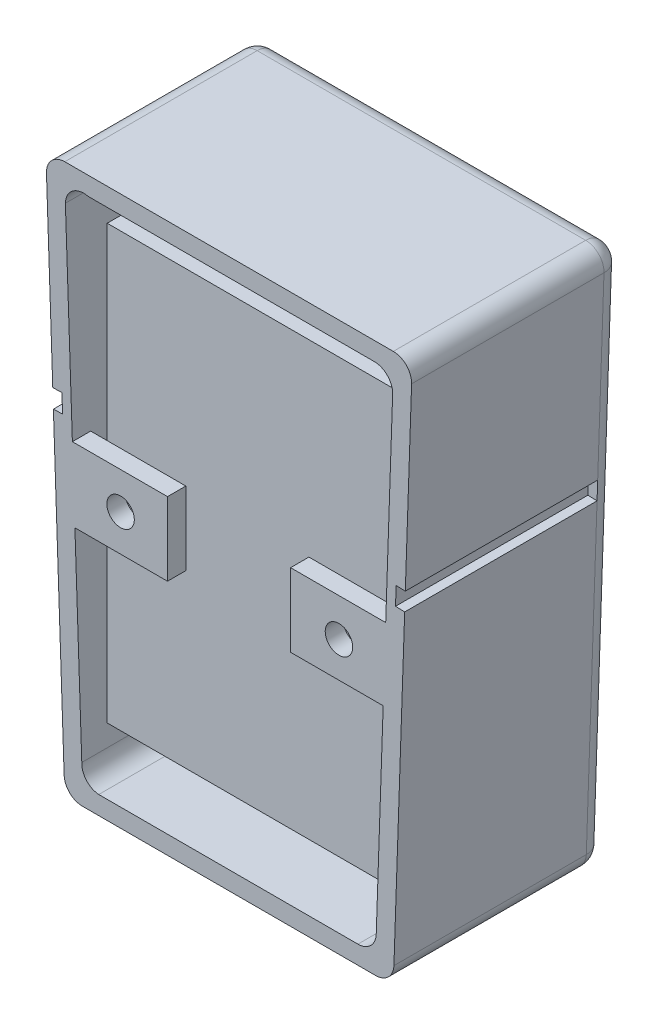
SolidWorks part; units mm, degrees
ref_plane "Front Plane" through (0, 0, 0) normal (0, 0, 1) x (1, 0, 0)
ref_plane "Top Plane" through (0, 0, 0) normal (0, 1, 0) x (1, 0, 0)
ref_plane "Right Plane" through (0, 0, 0) normal (1, 0, 0) x (0, 0, -1)
sketch "Sketch1" plane through (0, 0, 0) normal (0, 0, 1) x (1, 0, 0)
  line L8 (-22.7709, 76.1547) -> (22.7709, 76.1547)
  line L9 (25.3094, 73.5272) -> (22.8585, 2.4525)
  line L10 (20.32, 0) -> (-20.32, 0)
  line L11 (0, 76.1547) -> (0, 0) construction
  line L12 (-25.3094, 73.5272) -> (-22.8585, 2.4525)
  line L13 (-19.5413, 73.6147) -> (20.1418, 73.6147)
  line L14 (22.6803, 70.9872) -> (20.4046, 4.9925)
  line L15 (17.8661, 2.54) -> (-18.0612, 2.54)
  line L16 (-22.688, 71.2103) -> (-20.4122, 5.2126)
  arc A0 (22.8585, 2.4525) -> (20.32, 0) centre (20.32, 2.54) cw
  arc A1 (22.7709, 76.1547) -> (25.3094, 73.5272) centre (22.7709, 73.6147) cw
  arc A2 (-22.8585, 2.4525) -> (-20.32, 0) centre (-20.32, 2.54) ccw
  arc A3 (-22.7709, 76.1547) -> (-25.3094, 73.5272) centre (-22.7709, 73.6147) ccw
  circle A4 centre (0, 58.5396) radius 3.75
  circle A5 centre (0, 21.6223) radius 12.75
  arc A6 (20.4046, 4.9925) -> (17.8661, 2.54) centre (17.8661, 5.08) cw
  arc A7 (20.1418, 73.6147) -> (22.6803, 70.9872) centre (20.1418, 71.0747) cw
  arc A8 (-20.4122, 5.2126) -> (-18.0612, 2.54) centre (-17.876, 5.0732) ccw
  arc A9 (-19.5413, 73.6147) -> (-22.688, 71.2103) centre (-20.1487, 71.1484) ccw
  point P6 (22.7739, 0)
  point P9 (25.4, 76.1547)
  dimension "D2" = 76.2
  dimension "D3" = 2.54
  dimension "D5" = 7.5
  dimension "D6" = 24.7778
  dimension "D7" = 25.5
  dimension "D8" = 23.5056
  dimension "D12" = 2.54
  dimension "D13" = 2.54
  dimension "D15" = 2.54
  dimension "D1" = 25.4
  dimension "D4" = 40.64
  dimension "D9" = 65.9947
  dimension "D10" = 2.54
  dimension "D11" = 2.54
  dimension "D14" = 2.54
  dimension "D16" = 5.0732
  dimension "D17" = 5.2126
  dimension "D18" = 71.1484
  dimension "D19" = 71.2103
extrude "Boss-Extrude1" add sketch "Sketch1" along normal blind 3.81 contours L11 L13 A9 L16 A8 L15 A5 A4 | L13 L11 A4 A5 L15 A6 L14 A7 | L11 L8 A3 L12 A2 L10 L15 A8 L16 A9 L13 | L8 L11 L13 A7 L14 A6 L15 L10 A0 L9 A1 region at (-11.3855, 75.3522, 0) region at (11.3855, 75.3522, 0) region at (12.0205, 41.8931, 0) region at (-12.0224, 41.8976, 0)
ref_plane "Plane1" through (0, 0, 3.81) normal (0, 0, 1) x (1, 0, 0)
sketch "Sketch4" plane through (0, 0, 3.81) normal (0, 0, 1) x (1, 0, 0)
  line L8 (-22.7709, 76.1547) -> (22.7709, 76.1547)
  line L9 (25.3094, 73.5272) -> (22.8585, 2.4525)
  line L10 (20.32, 0) -> (-20.32, 0)
  line L11 (0, 76.1547) -> (0, 0) construction
  line L12 (-25.3094, 73.5272) -> (-22.8585, 2.4525)
  line L13 (-19.5413, 73.6147) -> (20.1418, 73.6147)
  line L14 (22.6803, 70.9872) -> (20.4046, 4.9925)
  line L15 (17.8661, 2.54) -> (-18.0612, 2.54)
  line L16 (-22.688, 71.2103) -> (-20.4122, 5.2126)
  arc A0 (22.8585, 2.4525) -> (20.32, 0) centre (20.32, 2.54) cw
  arc A1 (22.7709, 76.1547) -> (25.3094, 73.5272) centre (22.7709, 73.6147) cw
  arc A2 (-22.8585, 2.4525) -> (-20.32, 0) centre (-20.32, 2.54) ccw
  arc A3 (-22.7709, 76.1547) -> (-25.3094, 73.5272) centre (-22.7709, 73.6147) ccw
  arc A6 (20.4046, 4.9925) -> (17.8661, 2.54) centre (17.8661, 5.08) cw
  arc A7 (20.1418, 73.6147) -> (22.6803, 70.9872) centre (20.1418, 71.0747) cw
  arc A8 (-20.4122, 5.2126) -> (-18.0612, 2.54) centre (-17.876, 5.0732) ccw
  arc A9 (-19.5413, 73.6147) -> (-22.688, 71.2103) centre (-20.1487, 71.1484) ccw
  point P6 (22.7739, 0)
  point P9 (25.4, 76.1547)
  dimension "D2" = 76.2
  dimension "D3" = 2.54
  dimension "D5" = 5.0732
  dimension "D6" = 5.2126
  dimension "D7" = 71.1484
  dimension "D8" = 71.2103
  dimension "D12" = 2.54
  dimension "D13" = 2.54
  dimension "D15" = 2.54
  dimension "D16" = 0
  dimension "D1" = 25.4
  dimension "D4" = 40.64
  dimension "D9" = 65.9947
  dimension "D10" = 2.54
  dimension "D11" = 2.54
  dimension "D14" = 2.54
extrude "Boss-Extrude3" add sketch "Sketch4" along normal blind 25.4
ref_plane "Plane2" through (0, 0, 13.335) normal (0, 0, 1) x (1, 0, 0)
sketch "Sketch7" plane through (0, 0, 13.335) normal (0, 0, 1) x (1, 0, 0)
  line L11 (0, 76.1547) -> (0, 0) construction
  line L13 (-19.5377, 73.6147) -> (20.1453, 73.6147)
  line L14 (22.6838, 70.9872) -> (20.4081, 4.9925)
  line L15 (17.8696, 2.54) -> (-18.0576, 2.54)
  line L16 (-22.6652, 71.1077) -> (-20.3894, 5.1099)
  line L17 (20.1418, 73.6147) -> (-19.5413, 73.6147) construction
  arc A6 (20.4081, 4.9925) -> (17.8696, 2.54) centre (17.8696, 5.08) cw
  arc A7 (20.1453, 73.6147) -> (22.6838, 70.9872) centre (20.1453, 71.0747) cw
  arc A8 (-20.3894, 5.1099) -> (-18.0576, 2.54) centre (-17.8497, 5.0715) ccw
  arc A9 (-19.5377, 73.6147) -> (-22.6652, 71.1077) centre (-20.1255, 71.1437) ccw
  point P6 (22.7739, 0)
  point P9 (25.4, 76.1547)
  dimension "D2" = 39.6831
  dimension "D3" = 65.9978
  dimension "D5" = 1.975
  dimension "D6" = 1.975
  dimension "D7" = 0
  dimension "D8" = 20.2239
  dimension "D12" = 2.54
  dimension "D13" = 2.54
  dimension "D15" = 2.54
  dimension "D11" = 20.1255
  dimension "D4" = 35.9272
  dimension "D9" = 65.9947
  dimension "D10" = 20.2012
extrude "Boss-Extrude4" add sketch "Sketch7" along normal blind 2.54
fillet "Fillet1" radius 2.54 8 edges at (0, 76.1547, 0) (-24.5976, 75.3796, 0) (-24.0839, 37.9898, 0) (-22.0848, 0.7133, 0) (0, 0, 0) (22.0848, 0.7133, 0) (24.0839, 37.9898, 0) (24.5976, 75.3796, 0)
sketch "Sketch8" plane through (0, 0, 29.21) normal (0, 0, 1) x (1, 0, 0)
  line L0 (-24.0839, 37.9898) -> (24.0839, 37.9898) construction
  line L1 (-25.3094, 73.5272) -> (-22.8585, 2.4525) construction
  line L2 (22.8585, 2.4525) -> (25.3094, 73.5272) construction
  line L3 (-21.3673, 32.9098) -> (-21.7176, 43.0698) construction
  line L4 (-22.688, 71.2103) -> (-20.4122, 5.2126) construction
  line L5 (-21.7176, 43.0698) -> (-8.5315, 43.0698)
  line L6 (-8.5315, 43.0698) -> (-8.5315, 32.9098)
  line L7 (-8.5315, 32.9098) -> (-21.3673, 32.9098)
  line L9 (0, 76.1547) -> (0, 0) construction
  line L10 (22.7709, 76.1547) -> (-22.7709, 76.1547) construction
  line L11 (-20.32, 0) -> (20.32, 0) construction
  line L12 (8.5315, 32.9098) -> (21.3673, 32.9098)
  line L13 (8.5315, 43.0698) -> (8.5315, 32.9098)
  line L14 (21.7176, 43.0698) -> (8.5315, 43.0698)
  line L15 (-21.3673, 32.9098) -> (-21.7176, 43.0698)
  line L16 (21.3673, 32.9098) -> (21.7176, 43.0698)
  dimension "D1" = 5.08
  dimension "D2" = 5.08
  dimension "D3" = 17.0629
extrude "Boss-Extrude6" add sketch "Sketch8" against normal blind 2.54
sketch "Sketch9" plane through (0, 0, 29.21) normal (0, 0, 1) x (1, 0, 0)
  line L0 (-15.1245, 43.0698) -> (-14.9494, 32.9098) construction
  line L1 (-8.5315, 43.0698) -> (-21.7176, 43.0698) construction
  line L2 (-21.3673, 32.9098) -> (-8.5315, 32.9098) construction
  line L3 (0.3003, 73.6147) -> (-0.0975, 2.54) construction
  line L4 (20.1418, 73.6147) -> (-19.5413, 73.6147) construction
  line L5 (-18.0612, 2.54) -> (17.8661, 2.54) construction
  circle A0 centre (-15.0369, 37.9898) radius 1.905
  circle A1 centre (15.2377, 37.8204) radius 1.905
  dimension "D1" = 3.81
extrude "Cut-Extrude1" cut sketch "Sketch9" against normal blind 2.54
sketch "Sketch10" plane through (0, 0, 0) normal (0, 0, -1) x (-1, 0, 0)
  line L0 (0, 73.6147) -> (0, 2.54) construction
  line L1 (22.7709, 73.6147) -> (-22.7709, 73.6147) construction
  line L2 (-20.32, 2.54) -> (20.32, 2.54) construction
  line L3 (-21.8533, 47.0045) -> (21.8533, 47.0045) construction
  line L4 (-22.7709, 73.6147) -> (-20.32, 2.54) construction
  line L5 (20.32, 2.54) -> (22.7709, 73.6147) construction
  line L6 (-21.8971, 48.2745) -> (21.8971, 48.2745)
  line L7 (21.8971, 48.2745) -> (21.8095, 45.7345)
  line L8 (21.8095, 45.7345) -> (-21.8095, 45.7345)
  line L9 (-21.8095, 45.7345) -> (-21.8971, 48.2745)
  dimension "D1" = 26.6102
  dimension "D2" = 1.27
  dimension "D3" = 1.27
extrude "Cut-Extrude2" cut sketch "Sketch10" against normal blind 1.27
sketch "Sketch11" plane through (-22.7469, -0.7844, 0) normal (-0.9994, -0.0345, 0) x (0, 0, 1)
  line L0 (2.54, 47.7456) -> (29.21, 47.7456) construction
  line L1 (2.54, 74.3558) -> (2.54, 3.2388) construction
  line L2 (29.21, 74.3558) -> (29.21, 3.2388) construction
  line L3 (29.21, 74.3558) -> (2.54, 74.3558) construction
  line L4 (2.54, 49.0156) -> (29.21, 49.0156)
  line L5 (29.21, 49.0156) -> (29.21, 46.4756)
  line L6 (29.21, 46.4756) -> (2.54, 46.4756)
  line L7 (2.54, 46.4756) -> (2.54, 49.0156)
  dimension "D1" = 26.6102
  dimension "D2" = 1.27
  dimension "D3" = 1.27
extrude "Cut-Extrude3" cut sketch "Sketch11" against normal blind 1.27
sketch "Sketch12" plane through (22.7469, -0.7844, 0) normal (0.9994, -0.0345, 0) x (0, 0, -1)
  line L0 (-29.21, 47.7456) -> (-2.54, 47.7456) construction
  line L1 (-29.21, 3.2388) -> (-29.21, 74.3558) construction
  line L2 (-2.54, 3.2388) -> (-2.54, 74.3558) construction
  line L3 (-29.21, 74.3558) -> (-2.54, 74.3558) construction
  line L4 (-2.54, 49.0156) -> (-29.21, 49.0156)
  line L5 (-29.21, 49.0156) -> (-29.21, 46.4756)
  line L6 (-29.21, 46.4756) -> (-2.54, 46.4756)
  line L7 (-2.54, 46.4756) -> (-2.54, 49.0156)
  dimension "D1" = 26.6102
  dimension "D2" = 1.27
  dimension "D3" = 1.27
extrude "Cut-Extrude4" cut sketch "Sketch12" against normal blind 1.27
sketch "Sketch13" plane through (0, 0, 15.875) normal (0, 0, 1) x (1, 0, 0)
  line L0 (0.3003, 73.6147) -> (0, 0) construction
  line L1 (-19.5413, 73.6147) -> (20.1418, 73.6147) construction
  line L2 (-20.066, 68.5347) -> (19.9136, 68.5347)
  line L3 (-20.066, 68.5347) -> (-20.066, 8.5399)
  line L4 (19.9136, 68.5347) -> (19.9136, 8.5399)
  line L5 (-20.066, 8.5399) -> (19.9136, 8.5399)
  line L6 (-20.32, 2.54) -> (-20.32, 65.1906) construction
  dimension "D1" = 39.9796
  dimension "D2" = 0.254
  dimension "D3" = 5.08
  dimension "D4" = 59.9948
extrude "Boss-Extrude7" add sketch "Sketch13" along normal blind 10.16
